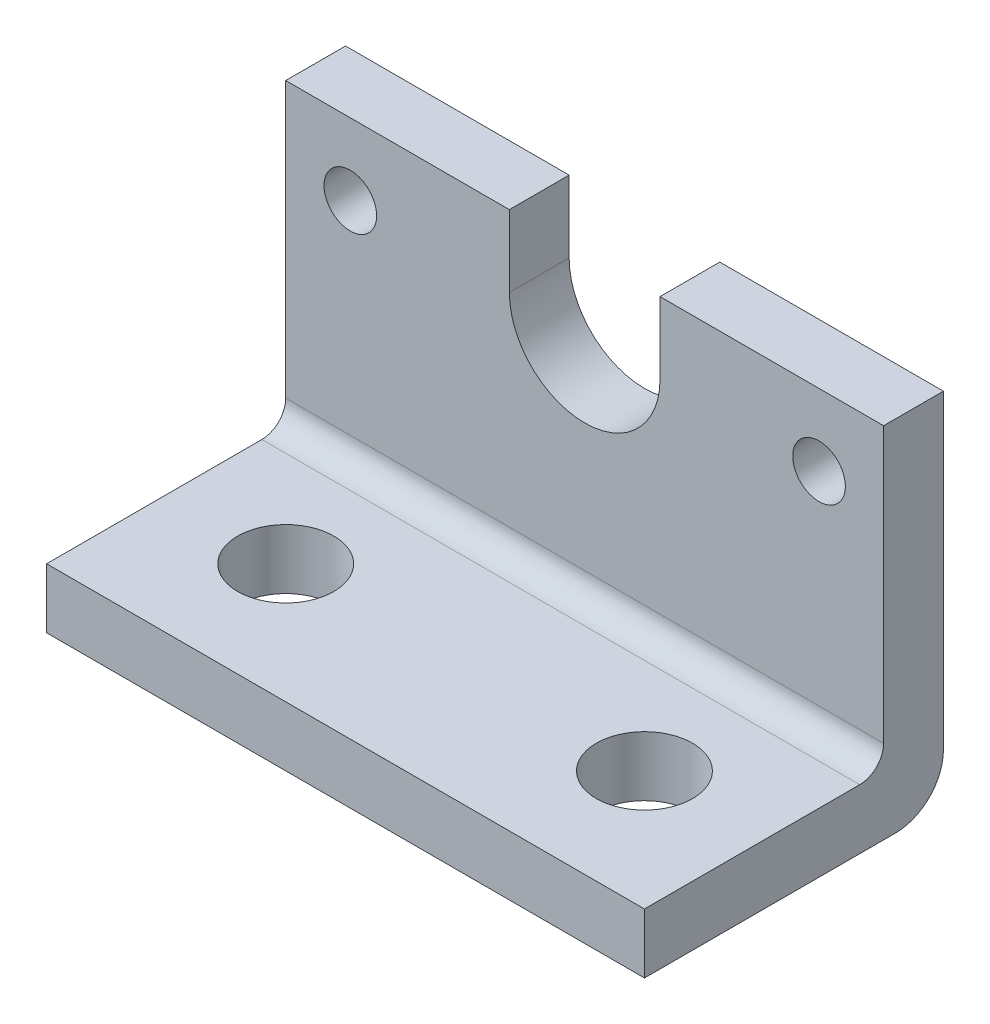
SolidWorks part; units mm, degrees
ref_plane "Front Plane" through (0, 0, 0) normal (0, 0, 1) x (1, 0, 0)
ref_plane "Top Plane" through (0, 0, 0) normal (0, 1, 0) x (1, 0, 0)
ref_plane "Right Plane" through (0, 0, 0) normal (1, 0, 0) x (0, 0, -1)
sketch "Sketch1" plane through (0, 0, 0) normal (0, 0, 1) x (1, 0, 0)
  line L0 (-4.0005, 15.24) -> (-4.0005, 19.05)
  line L1 (-15.875, 19.05) -> (-4.0005, 19.05)
  line L2 (-15.875, 19.05) -> (-15.875, 0)
  line L3 (-15.875, 0) -> (15.875, 0)
  line L4 (15.875, 19.05) -> (15.875, 0)
  line L5 (-15.875, 19.05) -> (15.875, 0) construction
  line L6 (-15.875, 0) -> (15.875, 19.05) construction
  line L7 (4.0005, 15.24) -> (4.0005, 19.05)
  line L8 (0, 15.24) -> (0, 23.3212) construction
  line L9 (4.0005, 19.05) -> (15.875, 19.05)
  arc A0 (-4.0005, 15.24) -> (4.0005, 15.24) centre (0, 15.24) ccw
  circle A1 centre (12.446, 15.24) radius 1.397
  circle A2 centre (-12.446, 15.24) radius 1.397
  point P0 (0, 9.525)
  dimension "D3" = 8.001
  dimension "D5" = 2.794
  dimension "D1" = 31.75
  dimension "D2" = 19.05
  dimension "D4" = 15.24
  dimension "D6" = 24.892
extrude "Boss-Extrude1" add sketch "Sketch1" against normal blind 3.175
sketch "Sketch2" plane through (0, 0, 0) normal (0, 1, 0) x (1, 0, 0)
  line L0 (0, -12.7) -> (0, 0) construction
  line L1 (-15.875, -12.7) -> (15.875, -12.7)
  line L2 (-15.875, -12.7) -> (-15.875, 0)
  line L3 (-15.875, 0) -> (15.875, 0)
  line L4 (15.875, -12.7) -> (15.875, 0)
  line L5 (-15.875, -12.7) -> (15.875, 0) construction
  line L6 (-15.875, 0) -> (15.875, -12.7) construction
  circle A0 centre (-9.525, -6.35) radius 2.5527
  circle A1 centre (9.525, -6.35) radius 2.5527
  point P0 (0, -6.35)
  dimension "D2" = 5.1054
  dimension "D1" = 12.7
  dimension "D3" = 19.05
extrude "Boss-Extrude2" add sketch "Sketch2" along normal blind 3.175
fillet "Fillet1" radius 1.27 1 edges
fillet "Fillet2" radius 2.54 1 edges at (0, 0, -3.175)
